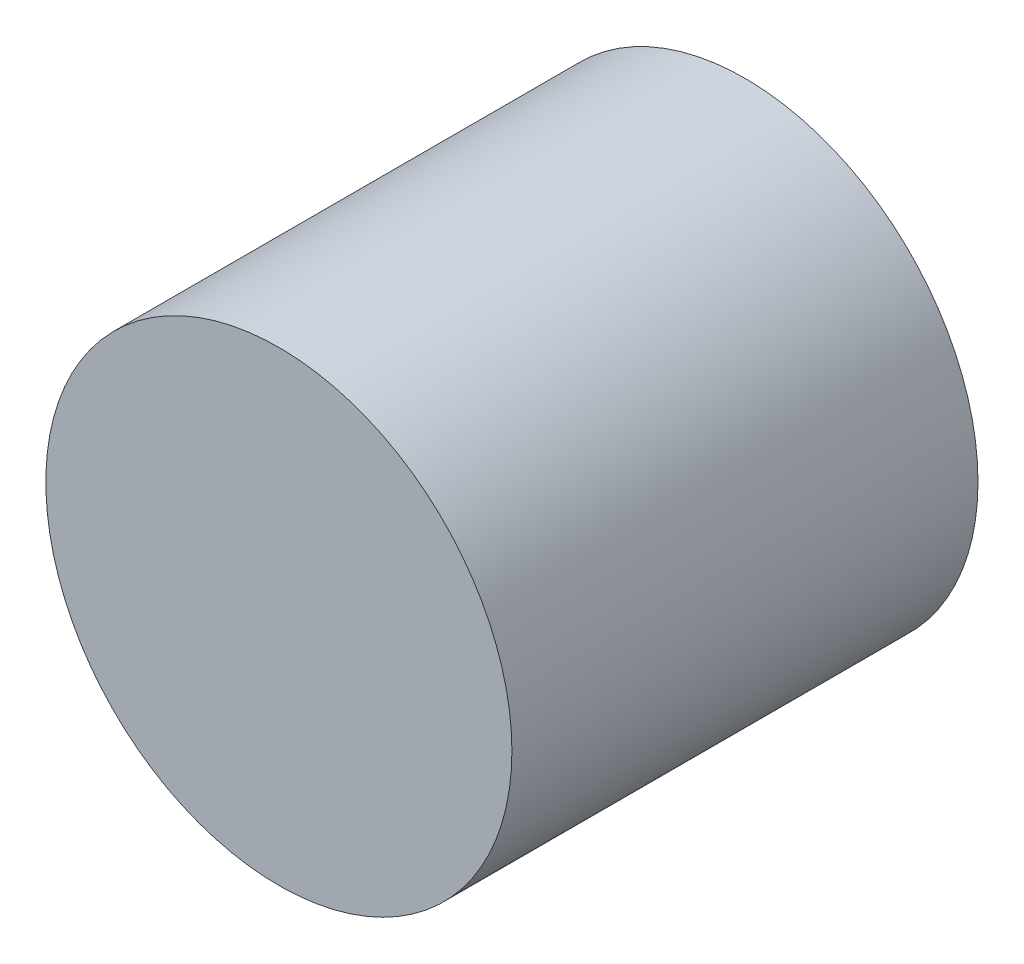
SolidWorks part; units mm, degrees
ref_plane "Спереди" through (0, 0, 0) normal (0, 0, 1) x (1, 0, 0)
ref_plane "Сверху" through (0, 0, 0) normal (0, 1, 0) x (1, 0, 0)
ref_plane "Справа" through (0, 0, 0) normal (1, 0, 0) x (0, 0, -1)
other "Configuration Table"
sketch "Проход_ровно6" plane through (0, 0, 0) normal (0, 0, 1) x (1, 0, 0)
  circle A0 centre (0, 0) radius 3
  dimension "Диаметр1" = 6
extrude "Цилиндр_6" add sketch "Проход_ровно6" along normal blind 6
equation "\"D1@Цилиндр_6\" = \"Толщина тонких панелей\""
equation "\"Фанера\"=6"
equation "\"Ширина шипа\"=16"
equation "\"Межосевое шипов\"=40"
equation "\"Посадочный зазор\"=0.15"
equation "\"Основная фреза\"=6"
equation "\"Мелкая фреза\"=6"
equation "\"Запас разгрузки\"=0.05"
equation "\"Ширина образца\"=84"
equation "\"Высота образца\"=50"
equation "\"Канал М6\"=6"
equation "\"Гайка под ключ\"=10.3"
equation "\"Длина кармана гайки\"=6.2"
equation "\"Отступ гайки\"=12"
equation "\"Диаметр1@Проход_ровно6\" = \"Канал М6\""
equation "\"Ширина груза\"= 420"
equation "\"Глубина груза\"= 490"
equation "\"Высота груза\"= 297"
equation "\"Ширина ячейки\"= \"Ширина груза\" + 10"
equation "\"Глубина ячейки\"= \"Глубина груза\" + 10"
equation "\"Высота ячейки\"= \"Высота груза\" + 10 + 13"
equation "\"Колво ячеек ширина\"= 2"
equation "\"Колво ячеек высота\"= 2"
equation "\"Толщина стенки\" = \"Толщина тонких панелей\""
equation "\"Крепление дверцы\"= 5 "
equation "\"Ширина рейки\"= \"Толщина шестерни\""
equation "\"Высота рейки\"= 20"
equation "\"Высота пола\" = 2*\"Толщина тонких панелей\""
equation "\"Колво полозьев\"= 5"
equation "\"Отступ рейки\"= 20"
equation "\"Глубина каретки\"= \"Глубина ячейки\" + 30 + \"Мотор Y высота корпуса\" + 20"
equation "\"Длинна рейки\" = (\"Ширина ячейки\"+\"Толщина вертикальных стенок\"+\"Крепление дверцы\")*\"Колво ячеек ширина\"+\"Ширина ячейки выгрузки\"*\"Колво выгрузки\"+\"Толщина вертикальных стенок\"+2*\"Отступ крепления мотора фиксации\"-\"Крепление дверцы\"*\"Колво ячеек ширина\""
equation "\"Отступ шпильки\"= 26"
equation "\"Диаметр шпильки\"= 5"
equation "\"Длинна шпильки\" = (\"Высота ячейки\"+\"Толщина горизонтальных плит\"+\"Высота пола\")*\"Колво ячеек высота\"+2*(\"Толщина горизонтальных плит\"+\"Отступ рейки\")"
equation "\"Ширина пластины\"= 50  "
equation "\"Высота зона выгрузки\"= \"Высота ячейки\" * 2 + \"Толщина стенки\" * 2"
equation "\"Колво выгрузки\"= 1"
equation "\"Ширина ячейки выгрузки\" = \"Ширина ячейки\"+\"Толщина вертикальных стенок\"+2*\"Отступ крепления мотора фиксации\""
equation "\"Отступ крепления мотора фиксации\" = (\"Ширина пластины\"+20-\"Толщина вертикальных стенок\")/2"
equation "\"Мотор X ширина корпуса\"= 42.3"
equation "\"Мотор X высота корпуса\"= 42.3"
equation "\"Мотор X длина корпуса\"= 40"
equation "\"Мотор X вылет вала\"= 19.8"
equation "\"Мотор Y ширина корпуса\"= 42.3"
equation "\"Мотор Y высота корпуса\"= 42.3"
equation "\"Мотор Y длина корпуса\"= 48"
equation "\"Мотор Y вылет вала\"= 30"
equation "\"Мотор Z ширина корпуса\"= 42"
equation "\"Мотор Z высота корпуса\"= 42"
equation "\"Мотор Z длина корпуса\"= 40"
equation "\"Мотор Z вылет вала\"= 23"
equation "\"Мотор диаметр вала ПРЕДВ\"= 5"
equation "\"Мотор шаг крепления ПРЕДВ\"= 31"
equation "\"Мотор диаметр отверстий ПРЕДВ\"= 3"
equation "\"Мотор глубина отверстий ПРЕДВ\"= 4.5"
equation "\"Мотор диаметр буртика ПРЕДВ\"= 22"
equation "\"Мотор высота буртика ПРЕДВ\"= 2"
equation "\"Мотор диаметр шкива ПРЕДВ\"= 16"
equation "\"Мотор длина шкива ПРЕДВ\"= 12"
equation "\"Мотор отступ шкива ПРЕДВ\"= 5"
equation "\"Мотор X шаг градусов\"= 1.8"
equation "\"Мотор Y шаг градусов\"= 1.8"
equation "\"Мотор Z шаг градусов\"= 1.8"
equation "\"Мотор Y диаметр ротора\"= 25.78"
equation "\"Толщина шестерни\"= 10"
equation "\"Толщина тонких панелей\" = 6"
equation "\"Толщина вертикальных стенок\" = 18"
equation "\"Толщина горизонтальных плит\" = 18"
equation "\"Базовая высота корпуса\" = (\"Высота ячейки\"+\"Толщина тонких панелей\"+\"Высота пола\")*\"Колво ячеек высота\"+6*\"Толщина тонких панелей\"+\"Мотор X ширина корпуса\"+\"Мотор Y ширина корпуса\"+75"
equation "\"Высота корпуса\" = (\"Высота ячейки\"+\"Толщина горизонтальных плит\"+\"Высота пола\")*\"Колво ячеек высота\"+2*\"Толщина горизонтальных плит\"+4*\"Толщина тонких панелей\"+\"Мотор X ширина корпуса\"+\"Мотор Y ширина корпуса\"+75"
equation "\"Смещение центра корпуса\" = (\"Высота корпуса\"-\"Базовая высота корпуса\")/2-(\"Толщина горизонтальных плит\"-\"Толщина тонких панелей\")"
equation "\"Отметка пола\" = -\"Базовая высота корпуса\"/2+\"Толщина тонких панелей\""
equation "\"Отметка потолка\" = \"Отметка пола\"+\"Высота корпуса\"-2*\"Толщина горизонтальных плит\""
equation "\"Отметка верхней полки\" = \"Отметка потолка\"-(28+\"Толщина тонких панелей\")-\"Высота ячейки\"-\"Высота пола\""
equation "\"Отметка нижней полки\" = \"Отметка верхней полки\"-\"Высота ячейки\"-\"Высота пола\"-\"Толщина горизонтальных плит\""
